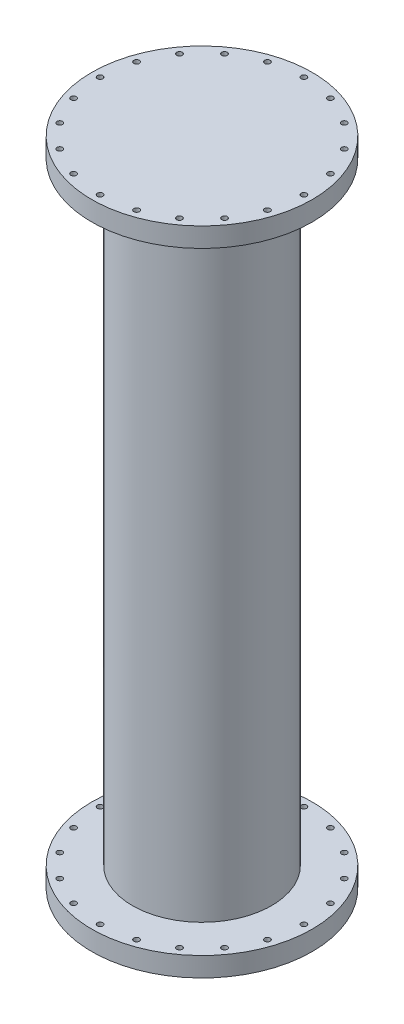
SolidWorks part; units mm, degrees
ref_plane "Plan de face" through (0, 0, 0) normal (0, 0, 1) x (1, 0, 0)
ref_plane "Plan de dessus" through (0, 0, 0) normal (0, 1, 0) x (1, 0, 0)
ref_plane "Plan de droite" through (0, 0, 0) normal (1, 0, 0) x (0, 0, -1)
sketch "Esquisse1" plane through (0, 0, 0) normal (0, 0, 1) x (1, 0, 0)
  line L0 (0, 0) -> (0, -1756.5308) construction
  line L1 (0, 0) -> (396, 0)
  line L2 (0, 0) -> (0, -70)
  line L3 (0, -70) -> (200, -70)
  line L4 (396, 0) -> (396, -70)
  line L26 (250, -70) -> (396, -70)
  line L27 (250, -2270) -> (396, -2270)
  line L29 (200, -70) -> (200, -2270)
  line L31 (250, -70) -> (250, -2270)
  line L32 (0, -2270) -> (200, -2270)
  line L33 (0, -2270) -> (0, -2340)
  line L34 (0, -2340) -> (396, -2340)
  line L35 (396, -2270) -> (396, -2340)
  dimension "D1" = 396
  dimension "D2" = 70
  dimension "D3" = 70
  dimension "D4" = 396
  dimension "D5" = 250
  dimension "D6" = 200
  dimension "D7" = 2200
revolve "Révolution1" add sketch "Esquisse1" angle 360 about L0
sketch "Esquisse2" plane through (0, 0, 0) normal (0, 1, 0) x (1, 0, 0)
  circle A0 centre (366, 0) radius 10
  dimension "D2" = 20
  dimension "D1" = 366
extrude "Enlèv. mat.-Extru.1" cut sketch "Esquisse2" against normal through all
pattern_circular "Répétition circulaire1" count 20 over 360 about axis through (0, 0, 0) along (0, 1, 0) of "Enlèv. mat.-Extru.1"
sketch "Esquisse3" plane through (0, -2340, 0) normal (0, 1, 0) x (1, 0, 0)
  circle A0 centre (0, 0) radius 255.3935
